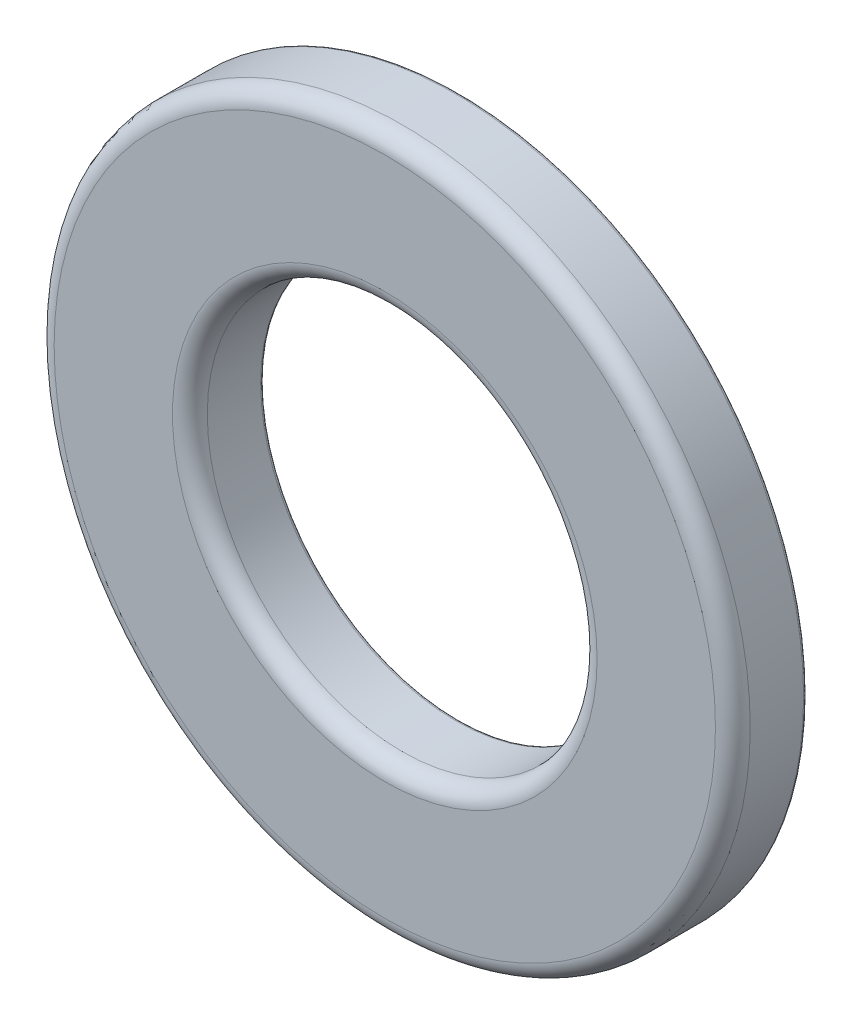
SolidWorks part; units mm, degrees
ref_plane "Front Plane" through (0, 0, 0) normal (0, 0, 1) x (1, 0, 0)
ref_plane "Top Plane" through (0, 0, 0) normal (0, 1, 0) x (1, 0, 0)
ref_plane "Right Plane" through (0, 0, 0) normal (1, 0, 0) x (0, 0, -1)
sketch "Sketch1" plane through (0, 0, 0) normal (0, 0, 1) x (1, 0, 0)
  circle A0 centre (0, 0) radius 7.5 construction
  circle A1 centre (0, 0) radius 4.2 construction
  point P6 (0, 7.5)
  dimension "OD" = 15
  dimension "ID" = 8.4
sketch "Sketch2" plane through (0, 0, 0) normal (1, 0, 0) x (0, 0, -1)
  line L1 (-0.8, 7.5) -> (0.8, 7.5) construction
  point P0 (-0.8, 7.5)
  point P3 (0.8, 7.5)
  point P11 (-0.8, 7.5)
  point P13 (0.8, 7.5)
  dimension "Thickness" = 1.6
sketch "Sketch3" plane through (0, 0, 0) normal (0, 0, 1) x (1, 0, 0)
  circle A0 centre (0, 0) radius 4.2 construction
  circle A1 centre (0, 0) radius 7.5 construction
  circle A2 centre (0, 0) radius 4.2
  circle A3 centre (0, 0) radius 7.5
extrude "Boss-Extrude1" add sketch "Sketch3" against normal up to vertex (0.8 mm away) and the other way up to vertex (0.8 mm away) up to point (0, 7.5, -0.8) other way up to point (0, 7.5, 0.8)
fillet "Fillet1" radius 0.375 2 edges at (4.2, 0, 0.8) (7.5, 0, 0.8)
fillet "Fillet3" radius 0.075 2 edges at (7.5, 0, -0.8) (4.2, 0, -0.8)
equation "\"D1@Fillet1\"=\"OD@Sketch1\"*.025"
equation "\"D1@Fillet2\"=\"OD@Sketch1\"*.02"
equation "\"D1@Fillet3\"=\"OD@Sketch1\"*.005"
